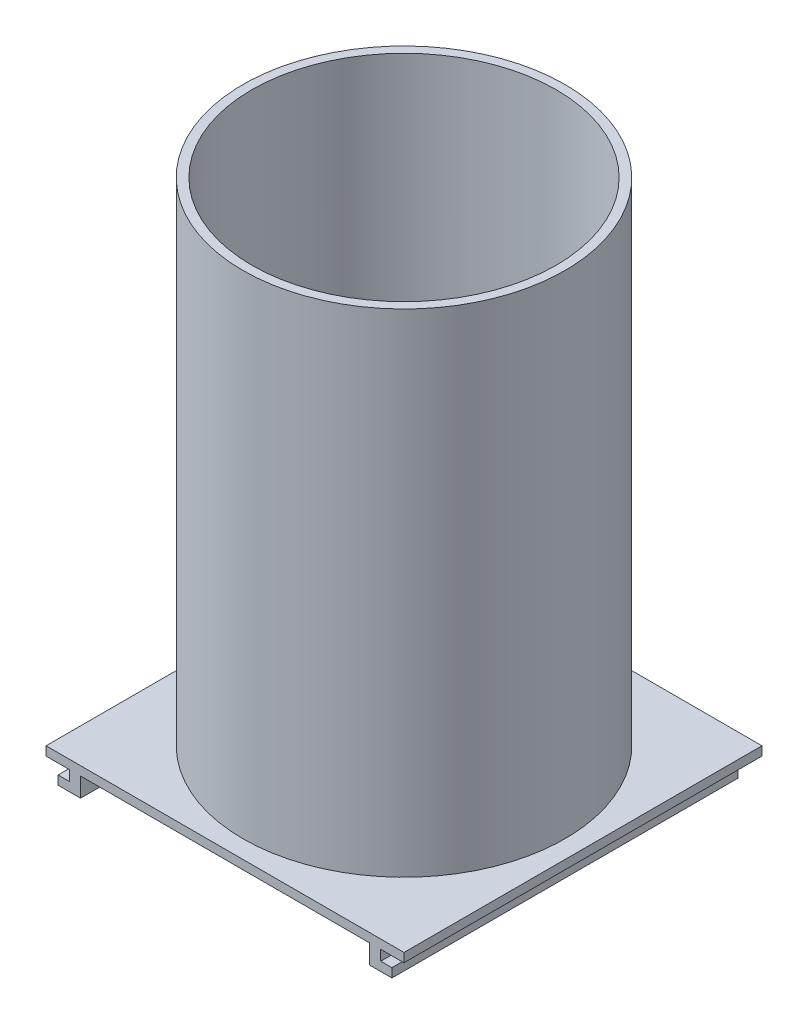
SolidWorks part; units mm, degrees
ref_plane "Front Plane" through (0, 0, 0) normal (0, 0, 1) x (1, 0, 0)
ref_plane "Top Plane" through (0, 0, 0) normal (0, 1, 0) x (1, 0, 0)
ref_plane "Right Plane" through (0, 0, 0) normal (1, 0, 0) x (0, 0, -1)
sketch "Sketch1" plane through (0, 0, 0) normal (0, 1, 0) x (1, 0, 0)
  line L1 (-40, -40) -> (40, -40)
  line L2 (-40, -40) -> (-40, 40)
  line L3 (-40, 40) -> (40, 40)
  line L4 (40, -40) -> (40, 40)
  line L5 (-40, -40) -> (40, 40) construction
  line L6 (-40, 40) -> (40, -40) construction
  circle A0 centre (0, 0) radius 34
  circle A1 centre (0, 0) radius 36
  point P0 (0, 0)
  dimension "D2" = 68
  dimension "D3" = 2
  dimension "D1" = 80
extrude "Boss-Extrude3" add sketch "Sketch1" against normal blind 2 contours L1 L4 L3 L2 A1 | A1 A0 region at (-38.8686, 0, 0) region at (-34.9818, 0, 0)
extrude "Boss-Extrude4" add sketch "Sketch1<7>" along normal blind 110 contours A1 A0 region at (-34.9818, 0, 0)
sketch "Sketch1<7>" plane through (0, 0, 0) normal (0, 1, 0) x (1, 0, 0) same geometry as "Sketch1"
sketch "Sketch3" plane through (0, 0, 40) normal (0, 0, 1) x (1, 0, 0)
  line L0 (-34.8, -2) -> (-32.3, -2)
  line L1 (-40, -2) -> (40, -2) construction
  line L2 (-32.3, -2) -> (-32.3, -6.3)
  line L3 (-32.3, -6.3) -> (-37.3, -6.3)
  line L4 (-37.3, -6.3) -> (-37.3, -4.3)
  line L5 (-37.3, -4.3) -> (-34.8, -4.3)
  line L6 (-34.8, -4.3) -> (-34.8, -2)
  line L8 (-40, -2) -> (-40, 0) construction
  line L9 (0, 0) -> (0, -6.3)
  line L10 (-40, 0) -> (40, 0) construction
  line L11 (37.3, -4.3) -> (34.8, -4.3)
  line L12 (37.3, -6.3) -> (37.3, -4.3)
  line L13 (32.3, -6.3) -> (37.3, -6.3)
  line L14 (32.3, -2) -> (32.3, -6.3)
  line L15 (34.8, -2) -> (32.3, -2)
  line L16 (34.8, -4.3) -> (34.8, -2)
  point P4 (-37.3, -5.3)
  line M10 (-40, -2) -> (40, -2)
  dimension "D1" = 2.5
  dimension "D2" = 2.7
  dimension "D3" = 2.3
  dimension "D4" = 2
  dimension "D5" = 2.5
extrude "Boss-Extrude5" add sketch "Sketch3" against normal offset from surface (77.35 mm away) 2.65 contours L6 L5 L4 L3 L2 M10 | L13 L12 L11 L16 L15 L14 region at (-34.3437, -4.5151, 40) up to face at (0, -1, -40)
